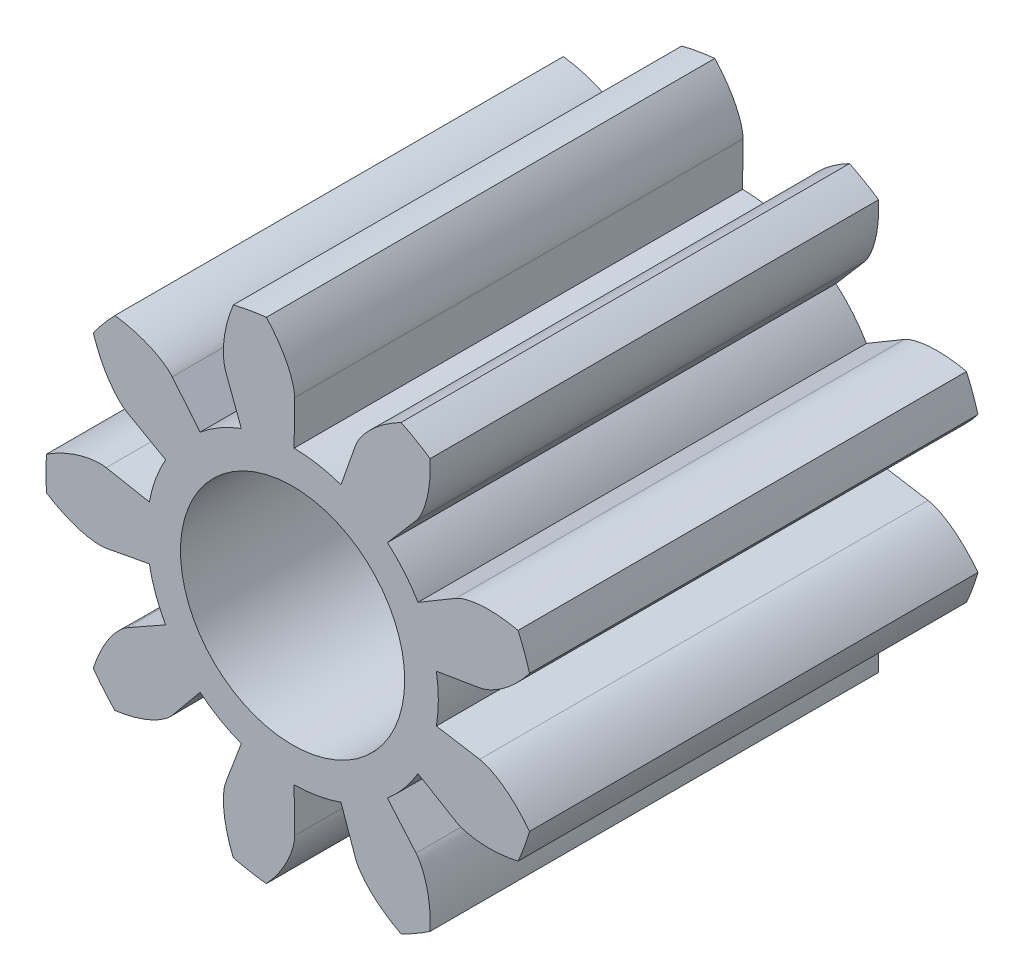
SolidWorks part; units mm, degrees
ref_plane "前视基准面" through (0, 0, 0) normal (0, 0, 1) x (1, 0, 0)
ref_plane "上视基准面" through (0, 0, 0) normal (0, 1, 0) x (1, 0, 0)
ref_plane "右视基准面" through (0, 0, 0) normal (1, 0, 0) x (0, 0, -1)
other "Configuration Table"
sketch "草图1" plane through (0, 0, 0) normal (0, 0, 1) x (1, 0, 0)
  line L0 (0, 0) -> (1.8, 0) construction
  line L1 (0, 0) -> (1.7727, 0.3126) construction
  line L2 (0, 0) -> (1.6688, 0.276)
  line L3 (1.7727, 0.3126) -> (1.7727, -0.3126) construction
  line L4 (0, 0) -> (1.6688, -0.276)
  circle A0 centre (0, 0) radius 2.2
  circle A1 centre (0, 0) radius 1.8 construction
  circle A2 centre (0, 0) radius 1.3
  circle A3 centre (0, 0) radius 1.6914 construction
  circle A4 centre (0, 0) radius 1
  spline S0 degree 4 poles (1.6688, 0.276) (1.6815, 0.2781) (1.7165, 0.2867) (1.7804, 0.3134) (1.8769, 0.3705) (1.9892, 0.4631) (2.115, 0.6012) (2.2366, 0.7836) (2.3401, 1.0009) (2.4181, 1.2482) (2.465, 1.503) (2.4828, 1.7615) (2.473, 2.0332) (2.4258, 2.3665) (2.3192, 2.7541) (2.1304, 3.1816) (1.8506, 3.6185) (1.5097, 4.0103) (1.1213, 4.3527) (0.6893, 4.6421) (0.2307, 4.8777) (-0.2607, 5.0574) (-0.7542, 5.1833) (-1.2841, 5.2523) (-1.6863, 5.2693) (-2.1385, 5.2469) (-2.3948, 5.2166) (-2.6865, 5.1734) (-2.8298, 5.138) (-2.9571, 5.1118) (-2.9949, 5.1006) (-3.0222, 5.094) (-3.037, 5.0905) knots 0 0 0 0 0 0.005604 0.015718 0.02996 0.048734 0.068727 0.096889 0.125051 0.153212 0.181374 0.209535 0.237696 0.271429 0.327752 0.384075 0.440398 0.496721 0.553044 0.609367 0.66569 0.722013 0.778336 0.834659 0.890982 0.909091 0.954545 0.977273 0.988636 0.994318 1 1 1 1 1 construction
  spline S1 degree 4 poles (1.6688, 0.276) (1.6815, 0.2781) (1.7165, 0.2867) (1.7804, 0.3134) (1.8769, 0.3705) (1.9892, 0.4631) (2.115, 0.6012) (2.2366, 0.7836) (2.3401, 1.0009) (2.4181, 1.2482) (2.465, 1.503) (2.4828, 1.7615) (2.473, 2.0332) (2.4258, 2.3665) (2.3192, 2.7541) (2.1304, 3.1816) (1.8506, 3.6185) (1.5097, 4.0103) (1.1213, 4.3527) (0.6893, 4.6421) (0.2307, 4.8777) (-0.2607, 5.0574) (-0.7542, 5.1833) (-1.2841, 5.2523) (-1.6863, 5.2693) (-2.0219, 5.2526) (-2.1774, 5.2392) (-2.215, 5.2356) knots 0 0 0 0 0 0.005604 0.015718 0.02996 0.048734 0.068727 0.096889 0.125051 0.153212 0.181374 0.209535 0.237696 0.271429 0.327752 0.384075 0.440398 0.496721 0.553044 0.609367 0.66569 0.722013 0.778336 0.834659 0.890982 0.909091 0.909091 0.909091 0.909091 0.909091
  spline S2 degree 4 poles (1.6688, -0.276) (1.6815, -0.2781) (1.7165, -0.2867) (1.7804, -0.3134) (1.8769, -0.3705) (1.9892, -0.4631) (2.115, -0.6012) (2.2366, -0.7836) (2.3401, -1.0009) (2.4181, -1.2482) (2.465, -1.503) (2.4828, -1.7615) (2.473, -2.0332) (2.4258, -2.3665) (2.3192, -2.7541) (2.1304, -3.1816) (1.8506, -3.6185) (1.5097, -4.0103) (1.1213, -4.3527) (0.6893, -4.6421) (0.2307, -4.8777) (-0.2607, -5.0574) (-0.7542, -5.1833) (-1.2841, -5.2523) (-1.6863, -5.2693) (-2.1385, -5.2469) (-2.3948, -5.2166) (-2.6865, -5.1734) (-2.8298, -5.138) (-2.9571, -5.1118) (-2.9949, -5.1006) (-3.0222, -5.094) (-3.037, -5.0905) knots 0 0 0 0 0 0.005604 0.015718 0.02996 0.048734 0.068727 0.096889 0.125051 0.153212 0.181374 0.209535 0.237696 0.271429 0.327752 0.384075 0.440398 0.496721 0.553044 0.609367 0.66569 0.722013 0.778336 0.834659 0.890982 0.909091 0.954545 0.977273 0.988636 0.994318 1 1 1 1 1 construction
  spline S3 degree 4 poles (1.6688, -0.276) (1.6815, -0.2781) (1.7165, -0.2867) (1.7804, -0.3134) (1.8769, -0.3705) (1.9892, -0.4631) (2.115, -0.6012) (2.2366, -0.7836) (2.3401, -1.0009) (2.4181, -1.2482) (2.465, -1.503) (2.4828, -1.7615) (2.473, -2.0332) (2.4258, -2.3665) (2.3192, -2.7541) (2.1304, -3.1816) (1.8506, -3.6185) (1.5097, -4.0103) (1.1213, -4.3527) (0.6893, -4.6421) (0.2307, -4.8777) (-0.2607, -5.0574) (-0.7542, -5.1833) (-1.2841, -5.2523) (-1.6863, -5.2693) (-2.0219, -5.2526) (-2.1774, -5.2392) (-2.215, -5.2356) knots 0 0 0 0 0 0.005604 0.015718 0.02996 0.048734 0.068727 0.096889 0.125051 0.153212 0.181374 0.209535 0.237696 0.271429 0.327752 0.384075 0.440398 0.496721 0.553044 0.609367 0.66569 0.722013 0.778336 0.834659 0.890982 0.909091 0.909091 0.909091 0.909091 0.909091
  point P15 (1.7727, 0)
  dimension "齿顶圆直径" = 4.4
  dimension "分度圆直径" = 3.6
  dimension "齿根圆直径" = 2.6
  dimension "基圆直径" = 3.3829
  dimension "内孔直径" = 2
  dimension "渐近线镜像线夹角" = 10
extrude "凸台-拉伸1" add sketch "草图1" along normal blind 4 contours A0 | A4
extrude "切除-拉伸1" cut sketch "草图1<3>" along normal through all contours A2 S3 A0 S1 region at (1.8185, 0, 0)
sketch "草图1<3>" plane through (0, 0, 0) normal (0, 0, 1) x (1, 0, 0) same geometry as "草图1"
pattern_circular "阵列(圆周)1" count 9 every 40 about axis through (0, 0, 4) along (0, 0, 1) of "切除-拉伸1"
equation "\"m\" = 0.4'模数"
equation "\"z\"= 9'齿数"
equation "\"a\" = 20度'压力角"
equation "\"d\"= \"m\" * \"z\"'分度圆直径"
equation "\"da\"= ( \"z\" + 2 ) * \"m\"'齿顶圆直径"
equation "\"df\"= ( \"z\" - 2.5 ) * \"m\"'齿根圆直径"
equation "\"s\"= 0.5 * PI * \"m\"'分度圆齿厚"
equation "\"r\"= 0.38 * \"m\"'齿根圆角"
equation "\"B\"= 0.3 * \"d\"'齿厚"
equation "\"db\"= \"m\" * \"z\" * cos ( \"a\" )'基圆直径"
equation "\"rb\"= \"db\" / 2'基圆半径"
equation "\"齿顶圆直径@草图1\"= \"da\""
equation "\"分度圆直径@草图1\"= \"d\""
equation "\"齿根圆直径@草图1\"= \"df\""
equation "\"基圆直径@草图1\"= \"db\""
equation "\"渐近线镜像线夹角@草图1\"= 360 / 4 / \"z\""
equation "\"h\"= 4mm'齿轮厚度"
equation "\"ir\"= 2mm'内孔直径"
equation "\"内孔直径@草图1\"= \"ir\""
equation "\"齿轮厚@凸台-拉伸1\"= \"h\""
equation "\"齿轮夹角@阵列(圆周)1\"= 360 / \"z\""
equation "\"齿数@阵列(圆周)1\"= \"z\""
